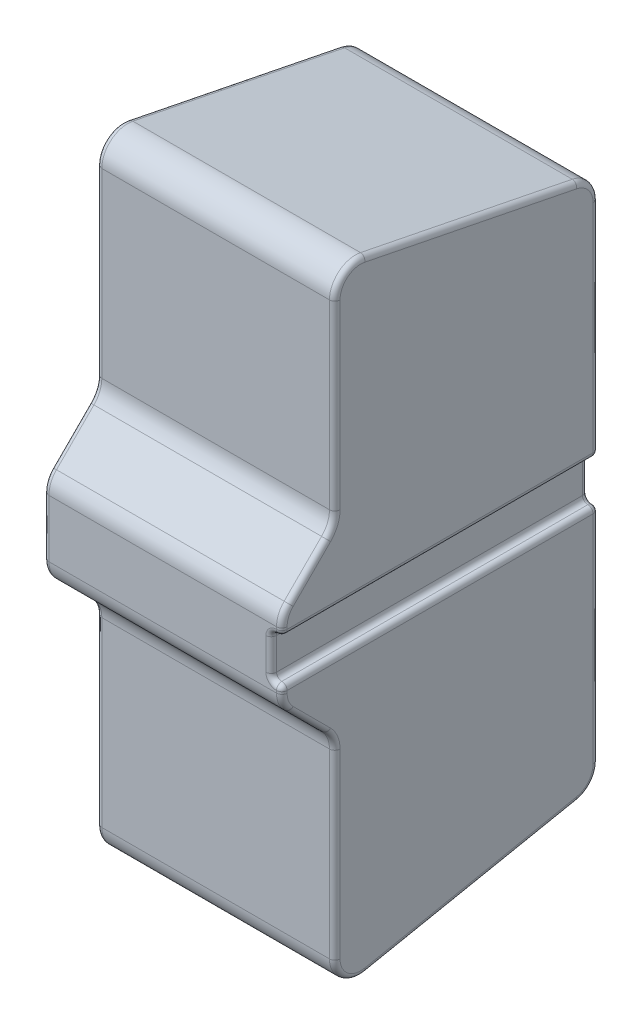
SolidWorks part; units mm, degrees
material "ABS"
ref_plane "Front Plane" through (0, 0, 0) normal (1, 0, 0) x (0, 1, 0)
ref_plane "Top Plane" through (0, 0, 0) normal (0, 0, 1) x (0, 1, 0)
ref_plane "Right Plane" through (0, 0, 0) normal (0, 1, 0) x (-1, 0, 0)
sketch "Sketch2" plane through (0, 0, 0) normal (1, 0, 0) x (0, 1, 0)
  line L0 (-0.8964, 2.3536) -> (-1.6036, 1.6464) construction
  line L1 (0.5429, 2.5) -> (-0.5429, 2.5) construction
  line L2 (1.6036, 1.6464) -> (0.8964, 2.3536) construction
  line L3 (5.3901, 1.5) -> (1.9571, 1.5) construction
  line L4 (5.0804, -3.0981) -> (5.8804, 0.9019) construction
  line L5 (-4.5901, -3.5) -> (4.5901, -3.5) construction
  line L6 (-5.8804, 0.9019) -> (-5.0804, -3.0981) construction
  line L7 (-1.9571, 1.5) -> (-5.3901, 1.5) construction
  line L8 (-0.8964, 2.3536) -> (-1.6036, 1.6464) construction
  line L9 (0.5429, 2.5) -> (-0.5429, 2.5) construction
  line L10 (1.6036, 1.6464) -> (0.8964, 2.3536) construction
  line L11 (5.3901, 1.5) -> (1.9571, 1.5) construction
  line L12 (5.0804, -3.0981) -> (5.8804, 0.9019) construction
  line L13 (-4.5901, -3.5) -> (4.5901, -3.5) construction
  line L14 (-5.8804, 0.9019) -> (-5.0804, -3.0981) construction
  line L15 (-1.9571, 1.5) -> (-5.3901, 1.5) construction
  line L16 (-0.4, 2.5) -> (-0.4, -3.5)
  line L17 (-0.4, -3.5) -> (0.0737, -3.5)
  line L18 (0, 0) -> (0, 4.4042) construction
  line L19 (0.4, 2.5) -> (0.4, -3.5)
  line L20 (-5.8706, 0.9039) -> (-5.0706, -3.0961)
  line L21 (-4.5901, -3.49) -> (4.5901, -3.49)
  line L22 (5.0706, -3.0961) -> (5.8706, 0.9039)
  line L23 (5.3901, 1.49) -> (1.9571, 1.49)
  line L24 (1.5965, 1.6394) -> (0.8894, 2.3465)
  line L25 (0.5429, 2.49) -> (-0.5429, 2.49)
  line L26 (-0.8894, 2.3465) -> (-1.5965, 1.6394)
  line L27 (-1.9571, 1.49) -> (-5.3901, 1.49)
  arc A0 (-1.9571, 1.5) -> (-1.6036, 1.6464) centre (-1.9571, 2) ccw construction
  arc A1 (-0.5429, 2.5) -> (-0.8964, 2.3536) centre (-0.5429, 2) ccw construction
  arc A2 (0.8964, 2.3536) -> (0.5429, 2.5) centre (0.5429, 2) ccw construction
  arc A3 (1.6036, 1.6464) -> (1.9571, 1.5) centre (1.9571, 2) ccw construction
  arc A4 (5.8804, 0.9019) -> (5.3901, 1.5) centre (5.3901, 1) ccw construction
  arc A5 (4.5901, -3.5) -> (5.0804, -3.0981) centre (4.5901, -3) ccw construction
  arc A6 (-5.0804, -3.0981) -> (-4.5901, -3.5) centre (-4.5901, -3) ccw construction
  arc A7 (-5.3901, 1.5) -> (-5.8804, 0.9019) centre (-5.3901, 1) ccw construction
  arc A8 (-1.9571, 1.5) -> (-1.6036, 1.6464) centre (-1.9571, 2) ccw construction
  arc A9 (-0.5429, 2.5) -> (-0.8964, 2.3536) centre (-0.5429, 2) ccw construction
  arc A10 (0.8964, 2.3536) -> (0.5429, 2.5) centre (0.5429, 2) ccw construction
  arc A11 (1.6036, 1.6464) -> (1.9571, 1.5) centre (1.9571, 2) ccw construction
  arc A12 (5.8804, 0.9019) -> (5.3901, 1.5) centre (5.3901, 1) ccw construction
  arc A13 (4.5901, -3.5) -> (5.0804, -3.0981) centre (4.5901, -3) ccw construction
  arc A14 (-5.0804, -3.0981) -> (-4.5901, -3.5) centre (-4.5901, -3) ccw construction
  arc A15 (-5.3901, 1.5) -> (-5.8804, 0.9019) centre (-5.3901, 1) ccw construction
  arc A16 (-5.0706, -3.0961) -> (-4.5901, -3.49) centre (-4.5901, -3) ccw
  arc A17 (4.5901, -3.49) -> (5.0706, -3.0961) centre (4.5901, -3) ccw
  arc A18 (5.8706, 0.9039) -> (5.3901, 1.49) centre (5.3901, 1) ccw
  arc A19 (1.5965, 1.6394) -> (1.9571, 1.49) centre (1.9571, 2) ccw
  arc A20 (0.8894, 2.3465) -> (0.5429, 2.49) centre (0.5429, 2) ccw
  arc A21 (-0.5429, 2.49) -> (-0.8894, 2.3465) centre (-0.5429, 2) ccw
  arc A22 (-1.9571, 1.49) -> (-1.5965, 1.6394) centre (-1.9571, 2) ccw
  arc A23 (-5.3901, 1.49) -> (-5.8706, 0.9039) centre (-5.3901, 1) ccw
  dimension "D1" = 0.4
  dimension "D2" = 0.01
extrude "Boss-Extrude2" add sketch "Sketch2" along normal blind 1.5 and the other way blind 3 contours L15 A15 L14 A14 L13 L16 L9 A9 L8 A8 region at (0, -2.8744, -0.8318)
extrude "Boss-Extrude3" add sketch "Sketch2<3>" along normal blind 1.3 and the other way blind 3 contours L19 L25 L16 L21 region at (0, 0, -0.5)
sketch "Sketch2<3>" plane through (0, 0, 0) normal (1, 0, 0) x (0, 1, 0) same geometry as "Sketch2"
mirror "Mirror1" about plane through (0, 0, 0) normal (0, 1, 0) of "Boss-Extrude2"
fillet "Fillet1" radius 0.1 40 edges at (1.3, 0, -3.49) (1.3, -0.4, -0.5) (1.3, 0, 2.49) (1.3, 0.4, -0.5) (1.5, 5.769, 1.3107) (1.5, 5.4706, -1.0961) (1.5, 4.9008, -3.3789) (1.5, 2.495, -3.49) (1.5, 0.4, -0.5) (1.5, 0.4714, 2.49) (1.5, 0.7304, 2.4527) (1.5, 1.2429, 1.9929) (1.5, 1.7619, 1.5288) (1.5, 3.6736, 1.49) (1.5, -1.7619, 1.5288) (1.5, -1.2429, 1.9929) (1.5, -0.7304, 2.4527) (1.5, -0.4714, 2.49) (1.5, -0.4, -0.5) (1.5, -2.495, -3.49) (1.5, -4.9008, -3.3789) (1.5, -5.4706, -1.0961) (1.5, -5.769, 1.3107) (1.5, -3.6736, 1.49) (-3, -5.769, 1.3107) (-3, -5.4706, -1.0961) (-3, -4.9008, -3.3789) (-3, 0, -3.49) (-3, 4.9008, -3.3789) (-3, 5.4706, -1.0961) (-3, 5.769, 1.3107) (-3, 3.6736, 1.49) (-3, 1.7619, 1.5288) (-3, 1.2429, 1.9929) (-3, 0.7304, 2.4527) (-3, 0, 2.49) (-3, -0.7304, 2.4527) (-3, -1.2429, 1.9929) (-3, -1.7619, 1.5288) (-3, -3.6736, 1.49)
